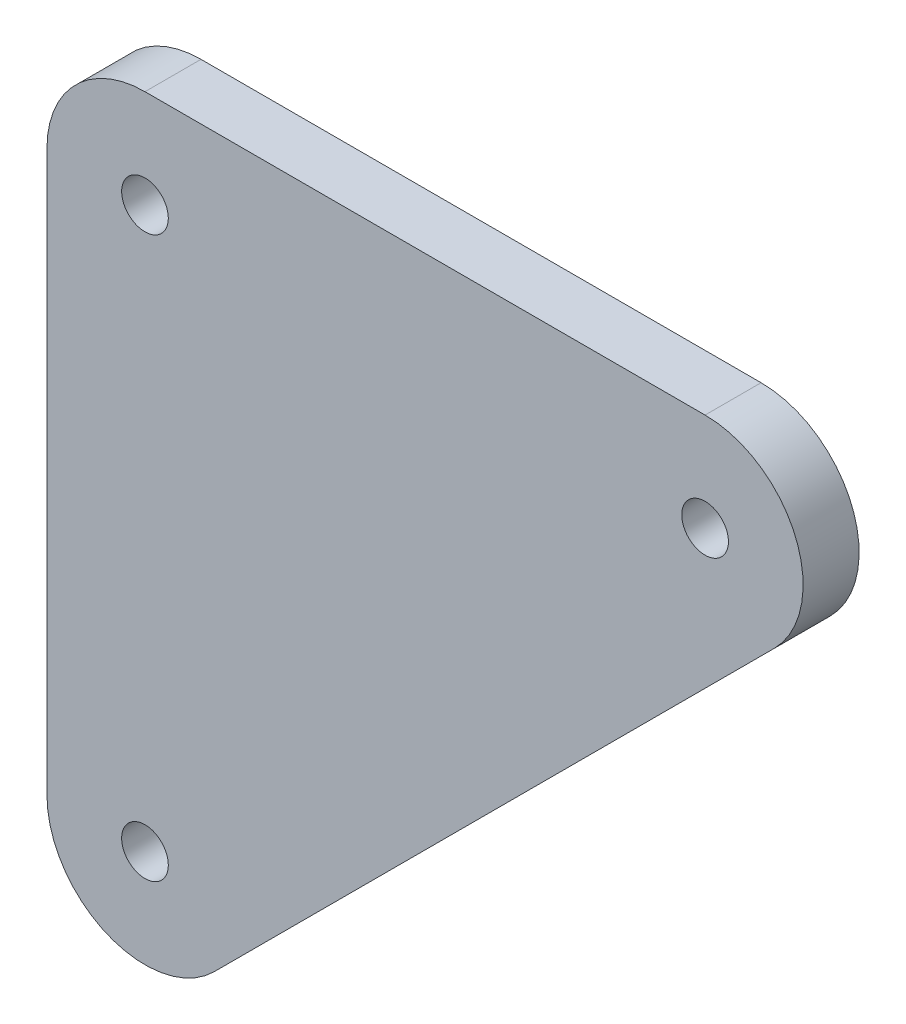
SolidWorks part; units mm, degrees
ref_plane "Plano frontal" through (0, 0, 0) normal (0, 0, 1) x (1, 0, 0)
ref_plane "Plano superior" through (0, 0, 0) normal (0, 1, 0) x (1, 0, 0)
ref_plane "Plano direito" through (0, 0, 0) normal (1, 0, 0) x (0, 0, -1)
sketch "Esboço1" plane through (0, 0, 0) normal (0, 0, 1) x (1, 0, 0)
  line L1 (-30, 30) -> (30, 30) construction
  line L2 (-30, 30) -> (-30, -30) construction
  line L3 (-30, -30) -> (30, -30) construction
  line L4 (30, 30) -> (30, -30) construction
  line L5 (-30, 30) -> (30, -30) construction
  line L6 (-30, -30) -> (30, 30) construction
  line L7 (-22.5754, -37.4246) -> (37.4246, 22.5754)
  line L8 (30, 40.5) -> (-30, 40.5)
  line L26 (-40.5, -30) -> (-40.5, 30)
  circle A0 centre (-30, 30) radius 2.5
  circle A1 centre (-30, -30) radius 2.5
  circle A2 centre (30, 30) radius 2.5
  arc A3 (-30, 40.5) -> (-40.5, 30) centre (-30, 30) ccw
  arc A4 (-40.5, -30) -> (-22.5754, -37.4246) centre (-30, -30) ccw
  arc A5 (37.4246, 22.5754) -> (30, 40.5) centre (30, 30) ccw
  circle A7 centre (30, 30) radius 10.5 construction
  circle A8 centre (-30, -30) radius 10.5 construction
  circle A9 centre (-30, 30) radius 10.5 construction
  point P0 (0, 0)
  point P13 (-20, 22.5)
  point P15 (-20, -22.5)
  point P20 (44, 0)
  point P34 (-81.0386, -15.474)
  point P36 (-81.0386, 15.2242)
  point P37 (-74.2886, -15.474)
  point P43 (-74.2886, 15.2242)
  dimension "D3" = 5
  dimension "D1" = 60
  dimension "D2" = 60
  dimension "D5" = 60
  dimension "D4" = 8
extrude "Ressalto-extrusão1" add sketch "Esboço1" along normal blind 6
